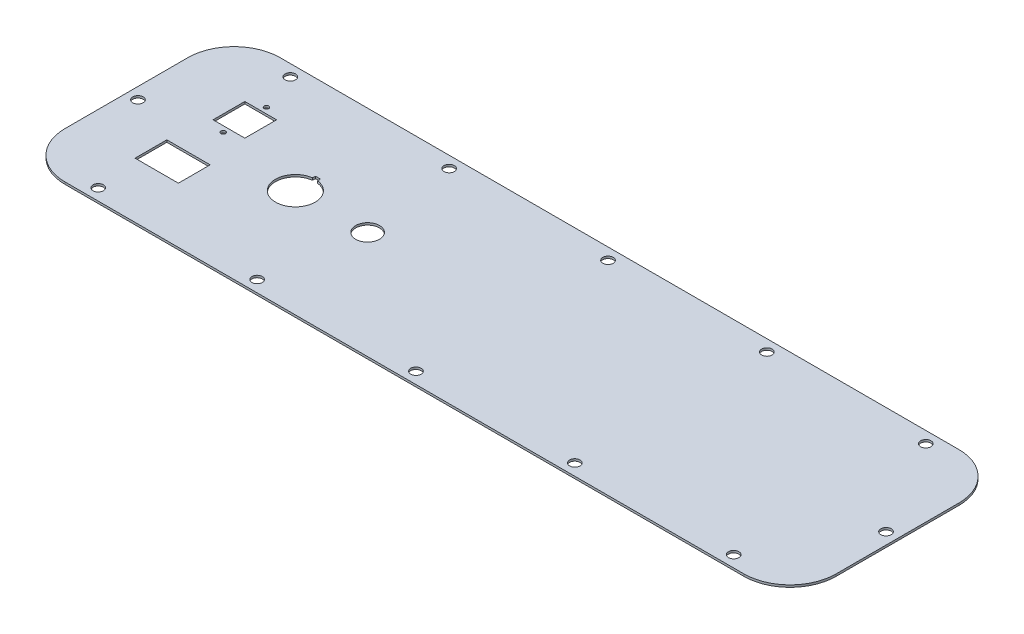
SolidWorks part; units mm, degrees
ref_plane "Front Plane" through (0, 0, 0) normal (0, 0, 1) x (1, 0, 0)
ref_plane "Top Plane" through (0, 0, 0) normal (0, 1, 0) x (1, 0, 0)
ref_plane "Right Plane" through (0, 0, 0) normal (1, 0, 0) x (0, 0, -1)
sketch "Sketch1" plane through (0, 0, 0) normal (0, 1, 0) x (1, 0, 0)
  line L0 (0, 0) -> (-259, 0) construction
  line L1 (235, -74.5) -> (-235, -74.5)
  line L2 (267, -42.5) -> (267, 42.5)
  line L3 (235, 74.5) -> (-235, 74.5)
  line L4 (-267, -42.5) -> (-267, 42.5)
  line L5 (267, -74.5) -> (-267, 74.5) construction
  line L6 (267, 74.5) -> (-267, -74.5) construction
  line L7 (0, 0) -> (259, 0) construction
  line L8 (220, 66.5) -> (-220, 66.5) construction
  line L9 (0, 66.5) -> (0, 0) construction
  line L10 (-220, 66.5) -> (-110, 66.5) construction
  arc A0 (-235, -74.5) -> (-267, -42.5) centre (-235, -42.5) cw
  arc A1 (267, -42.5) -> (235, -74.5) centre (235, -42.5) cw
  arc A2 (235, 74.5) -> (267, 42.5) centre (235, 42.5) cw
  arc A3 (-235, 74.5) -> (-267, 42.5) centre (-235, 42.5) ccw
  circle A4 centre (-259, 0) radius 3.6
  circle A5 centre (259, 0) radius 3.6
  circle A6 centre (-220, 66.5) radius 3.6
  circle A7 centre (-110, 66.5) radius 3.6
  circle A8 centre (0, 66.5) radius 3.6
  circle A9 centre (110, 66.5) radius 3.6
  circle A10 centre (220, 66.5) radius 3.6
  circle A11 centre (220, -66.5) radius 3.6
  circle A12 centre (110, -66.5) radius 3.6
  circle A13 centre (0, -66.5) radius 3.6
  circle A14 centre (-110, -66.5) radius 3.6
  circle A15 centre (-220, -66.5) radius 3.6
  point P0 (0, 0)
  point P26 (0, 66.5)
  dimension "D3" = 32
  dimension "D4" = 7.2
  dimension "D1" = 534
  dimension "D2" = 149
  dimension "D5" = 259
  dimension "D6" = 66.5
  dimension "D7" = 440
  dimension "D9" = 110
  dimension "D8" = 5
extrude "Boss-Extrude1" add sketch "Sketch1" along normal blind 1.5
sketch "Sketch2" plane through (0, 0, 0) normal (0, 1, 0) x (1, 0, 0)
  line L0 (-210, 25) -> (-210, -25) construction
  line L1 (-221, 14) -> (-199, 14)
  line L2 (-221, 14) -> (-221, 36)
  line L3 (-221, 36) -> (-199, 36)
  line L4 (-199, 14) -> (-199, 36)
  line L5 (-221, 14) -> (-199, 36) construction
  line L6 (-221, 36) -> (-199, 14) construction
  line L7 (-210, 10) -> (-210, 40) construction
  line L8 (-210, 14) -> (-210, 36) construction
  line L9 (-150, 0) -> (-150, 15.6382) construction
  line L10 (-210, -14) -> (-210, -36) construction
  line L11 (-151.75, 15.6382) -> (-148.25, 15.6382)
  line L12 (-151.75, 15.6382) -> (-151.75, 13.6382)
  line L14 (-148.25, 15.6382) -> (-148.25, 13.6382)
  line L15 (-195, -36) -> (-225, -36)
  line L16 (-195, -36) -> (-195, -14)
  line L17 (-195, -14) -> (-225, -14)
  line L18 (-225, -36) -> (-225, -14)
  line L19 (-195, -36) -> (-225, -14) construction
  line L20 (-195, -14) -> (-225, -36) construction
  line L23 (-210, 0) -> (0, 0) construction
  circle A0 centre (-210, 10) radius 1.6
  circle A1 centre (-210, 40) radius 1.6
  arc A2 (-151.75, 13.6382) -> (-148.25, 13.6382) centre (-150, 0) ccw
  arc A3 (-151.75, 13.6382) -> (-148.25, 13.6382) centre (-150, 0) cw construction
  circle A4 centre (-100, 0) radius 8.25
  point P0 (-210, 25)
  point P11 (-210, 25)
  point P22 (-150, 15.6382)
  point P32 (-210, 25)
  point P33 (-210, 0)
  dimension "D4" = 3.2
  dimension "D6" = 27.5
  dimension "D13" = 16.5
  dimension "D1" = 22
  dimension "D2" = 22
  dimension "D3" = 210
  dimension "D5" = 30
  dimension "D7" = 3.5
  dimension "D8" = 2
  dimension "D9" = 50
  dimension "D10" = 30
  dimension "D11" = 22
  dimension "D12" = 150
  dimension "D14" = 100
extrude "Cut-Extrude1" cut sketch "Sketch2" along normal through all
ref_plane "Plane1" through (-210, 0, 0) normal (1, 0, 0) x (0, 0, -1)
ref_plane "Plane2" through (-150, 0, 0) normal (1, 0, 0) x (0, 0, -1)
ref_plane "Plane3" through (-210, 0, 0) normal (1, 0, 0) x (0, 0, -1)
ref_plane "Plane4" through (0, 0, 25) normal (0, 0, 1) x (1, 0, 0)
ref_plane "Plane5" through (0, 0, -25) normal (0, 0, 1) x (1, 0, 0)
